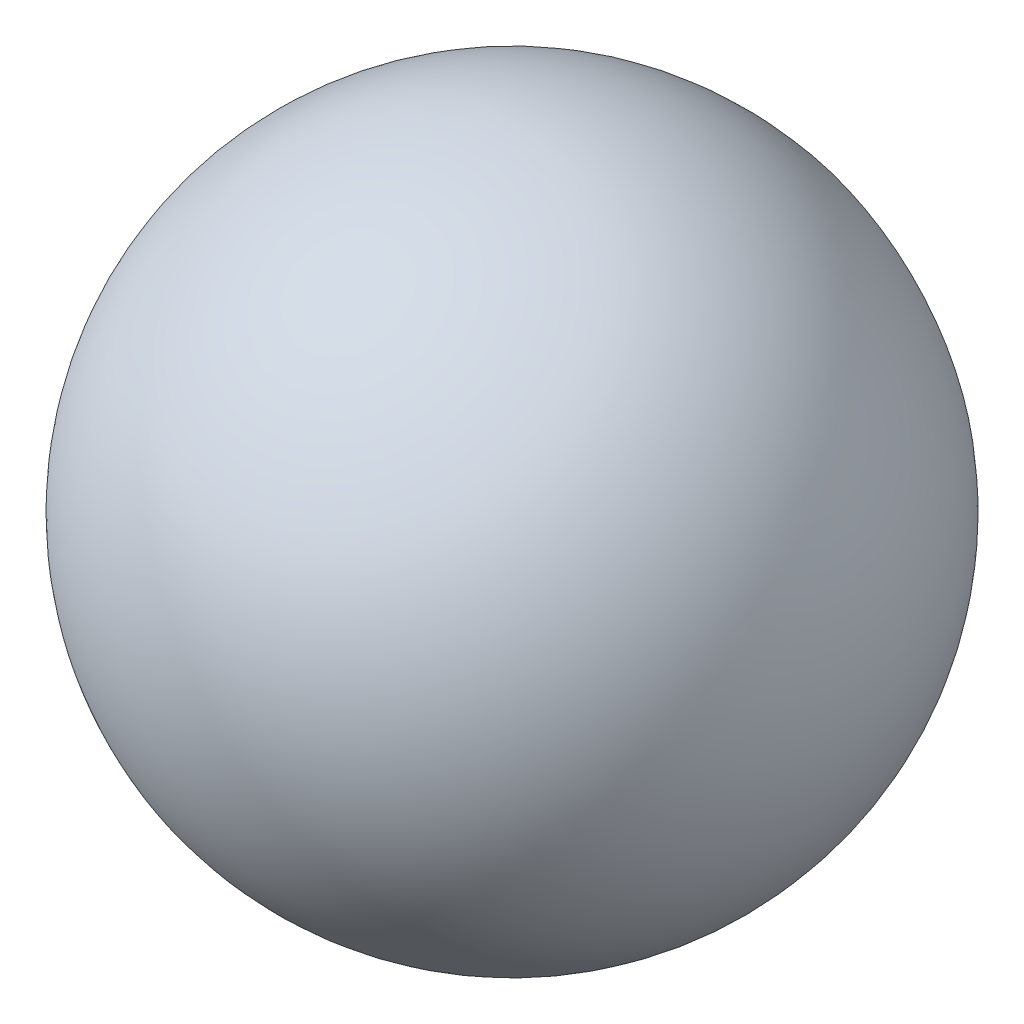
SolidWorks part; units mm, degrees
ref_plane "Front Plane" through (0, 0, 0) normal (0, 0, 1) x (1, 0, 0)
ref_plane "Top Plane" through (0, 0, 0) normal (0, 1, 0) x (1, 0, 0)
ref_plane "Right Plane" through (0, 0, 0) normal (1, 0, 0) x (0, 0, -1)
sketch "Sketch1" plane through (0, 0, 0) normal (0, 1, 0) x (1, 0, 0)
  line L0 (0, 58.4175) -> (0, -51.513) construction
  line L1 (0, 21.1148) -> (17.6186, 21.1148)
  line L2 (0, 21.1148) -> (0, -27.5)
  arc A0 (0, -27.5) -> (17.6186, 21.1148) centre (0, 0) ccw
  point P7 (0, 0)
  point P9 (0, 0)
  dimension "D1" = 55
revolve "Revolve1" add sketch "Sketch1" angle 360 about L0
